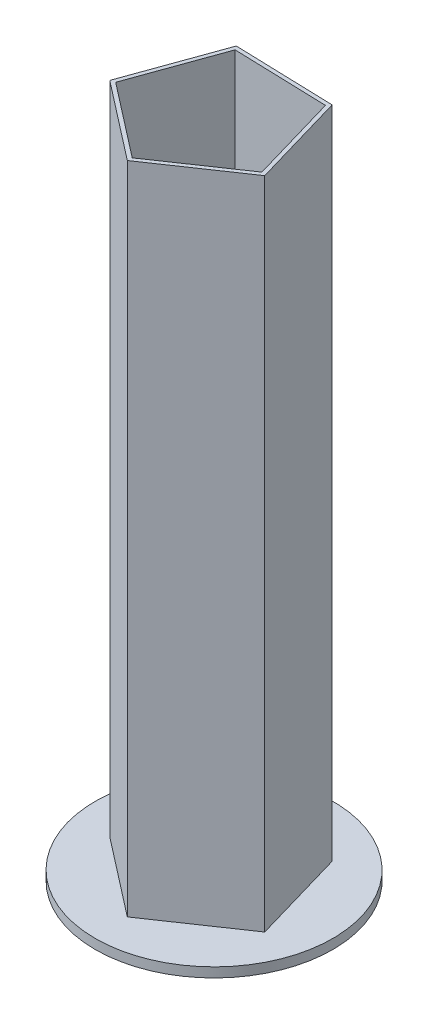
SolidWorks part; units mm, degrees
ref_plane "Front Plane" through (0, 0, 0) normal (0, 0, 1) x (1, 0, 0)
ref_plane "Top Plane" through (0, 0, 0) normal (0, 1, 0) x (1, 0, 0)
ref_plane "Right Plane" through (0, 0, 0) normal (1, 0, 0) x (0, 0, -1)
sketch "Sketch1" plane through (0, 0, 0) normal (0, 1, 0) x (1, 0, 0)
  circle A0 centre (0, 0) radius 37
  dimension "D1" = 74
extrude "Boss-Extrude1" add sketch "Sketch1" along normal blind 3
sketch "Sketch2" plane through (0, 3, 0) normal (0, 1, 0) x (1, 0, 0)
  line L0 (16.0579, 20.7082) -> (-14.7325, 21.6711)
  line L1 (23.2611, -8.3705) -> (15.1489, 19.536)
  line L2 (15.1489, 19.536) -> (-13.8986, 20.4445)
  line L3 (-13.8986, 20.4445) -> (-23.7387, -6.9006)
  line L4 (-23.7387, -6.9006) -> (-0.7728, -24.7093)
  line L5 (-0.7728, -24.7093) -> (23.2611, -8.3705)
  line L6 (-14.7325, 21.6711) -> (-25.163, -7.3147)
  line L7 (-25.163, -7.3147) -> (-0.8191, -26.1918)
  line L8 (-0.8191, -26.1918) -> (24.6568, -8.8728)
  line L9 (24.6568, -8.8728) -> (16.0579, 20.7082)
  circle A0 centre (0, 0) radius 20 construction
  dimension "D1" = 40
  dimension "D2" = 1.2
extrude "Boss-Extrude2" add sketch "Sketch2" along normal blind 204
